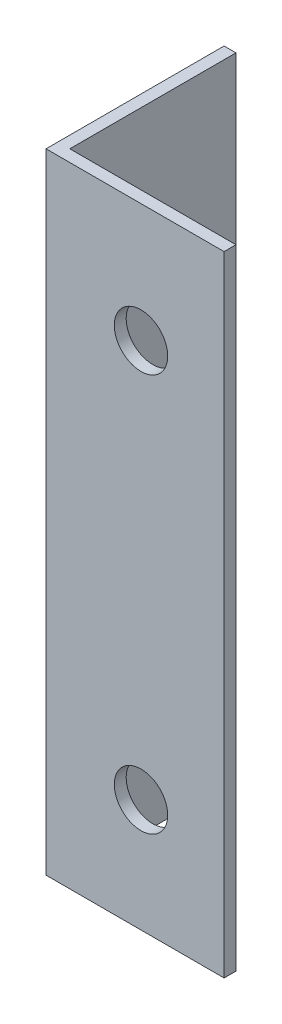
SolidWorks part; units mm, degrees
material "1060 Сплав"
ref_plane "Спереди" through (0, 0, 0) normal (0, 0, 1) x (1, 0, 0)
ref_plane "Сверху" through (0, 0, 0) normal (0, 1, 0) x (1, 0, 0)
ref_plane "Справа" through (0, 0, 0) normal (1, 0, 0) x (0, 0, -1)
sketch "Эскиз1" plane through (0, 0, 0) normal (0, 1, 0) x (1, 0, 0)
  line L0 (0, 0) -> (0, 15)
  line L1 (0, 15) -> (1, 15)
  line L2 (1, 15) -> (1, 1)
  line L3 (1, 1) -> (15, 1)
  line L4 (15, 1) -> (15, 0)
  line L5 (15, 0) -> (0, 0)
  dimension "D1" = 1
  dimension "D2" = 15
extrude "Бобышка-Вытянуть1" add sketch "Эскиз1" along normal blind 53
sketch "Эскиз2" plane through (0, 0, -1) normal (0, 0, -1) x (-1, 0, 0)
  line L0 (-8, 53) -> (-8, 0) construction
  line L1 (-15, 53) -> (-1, 53) construction
  line L2 (-15, 0) -> (-1, 0) construction
  circle A0 centre (-8, 43) radius 2.25
  circle A1 centre (-8, 9.5) radius 2.25
  dimension "D1" = 10
  dimension "D3" = 4.5
  dimension "D4" = 4.5
  dimension "D2" = 9.5
extrude "Вырез-Вытянуть1" cut sketch "Эскиз2" against normal through all
